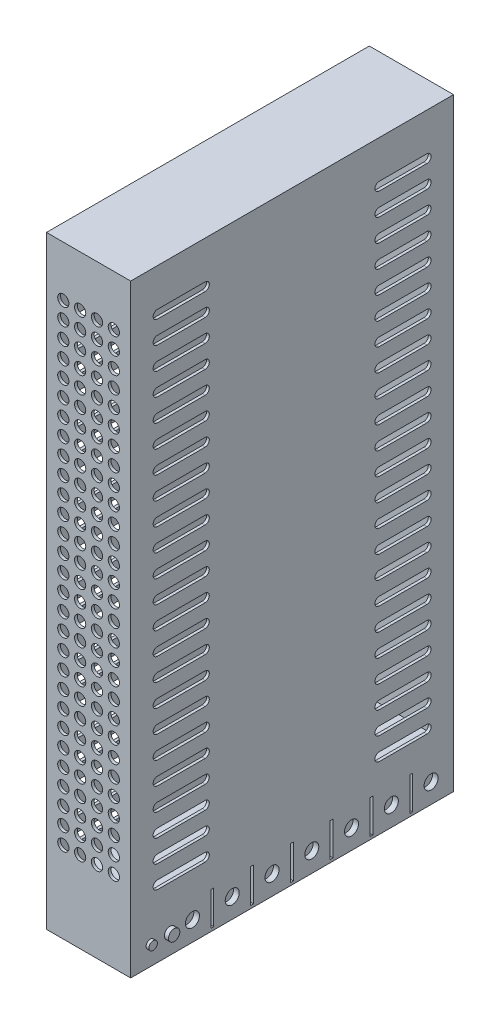
SolidWorks part; units mm, degrees
ref_plane "Front Plane" through (0, 0, 0) normal (0, 0, 1) x (1, 0, 0)
ref_plane "Top Plane" through (0, 0, 0) normal (0, 1, 0) x (1, 0, 0)
ref_plane "Right Plane" through (0, 0, 0) normal (1, 0, 0) x (0, 0, -1)
sketch "Sketch1" plane through (0, 0, 0) normal (0, 0, 1) x (1, 0, 0)
  line L1 (-15, 14) -> (15, 14)
  line L2 (-15, 14) -> (-15, 215)
  line L3 (-15, 215) -> (15, 215)
  line L4 (15, 14) -> (15, 215)
extrude "Case" add sketch "Sketch1" along normal blind 115
shell "Case_shell" thickness 1
sketch "Sketch2" plane through (0, 0, 0) normal (0, 0, 1) x (1, 0, 0)
  line L1 (-15, 0) -> (15, 0)
  line L2 (-15, 0) -> (-15, 14)
  line L3 (-15, 14) -> (15, 14)
  line L4 (15, 0) -> (15, 14)
extrude "Terminal_block" add sketch "Sketch2" along normal blind 115
ref_plane "Plane_x15" through (15, 0, 0) normal (1, 0, 0) x (0, 0, -1)
sketch "Sketch3" plane through (15, 0, 0) normal (1, 0, 0) x (0, 0, -1)
  circle A0 centre (-101, 7) radius 2
extrude "Pot" add sketch "Sketch3" along normal blind 1.5
sketch "Sketch4" plane through (15, 0, 0) normal (1, 0, 0) x (0, 0, -1)
  circle A0 centre (-108, 7) radius 1.5
extrude "LED" add sketch "Sketch4" along normal blind 1
ref_plane "Plane_z115" through (0, 0, 115) normal (0, 0, 1) x (1, 0, 0)
sketch "Sketch5" plane through (0, 0, 115) normal (0, 0, 1) x (1, 0, 0)
  circle A0 centre (-9, 29) radius 2
  circle A1 centre (-9, 35) radius 2
  circle A2 centre (-9, 41) radius 2
  circle A3 centre (-9, 47) radius 2
  circle A4 centre (-9, 53) radius 2
  circle A5 centre (-9, 59) radius 2
  circle A6 centre (-9, 65) radius 2
  circle A7 centre (-9, 71) radius 2
  circle A8 centre (-9, 77) radius 2
  circle A9 centre (-9, 83) radius 2
  circle A10 centre (-9, 89) radius 2
  circle A11 centre (-9, 95) radius 2
  circle A12 centre (-9, 101) radius 2
  circle A13 centre (-9, 107) radius 2
  circle A14 centre (-9, 113) radius 2
  circle A15 centre (-9, 119) radius 2
  circle A16 centre (-9, 125) radius 2
  circle A17 centre (-9, 131) radius 2
  circle A18 centre (-9, 137) radius 2
  circle A19 centre (-9, 143) radius 2
  circle A20 centre (-9, 149) radius 2
  circle A21 centre (-9, 155) radius 2
  circle A22 centre (-9, 161) radius 2
  circle A23 centre (-9, 167) radius 2
  circle A24 centre (-9, 173) radius 2
  circle A25 centre (-9, 179) radius 2
  circle A26 centre (-9, 185) radius 2
  circle A27 centre (-9, 191) radius 2
  circle A28 centre (-9, 197) radius 2
  circle A29 centre (-3, 29) radius 2
  circle A30 centre (-3, 35) radius 2
  circle A31 centre (-3, 41) radius 2
  circle A32 centre (-3, 47) radius 2
  circle A33 centre (-3, 53) radius 2
  circle A34 centre (-3, 59) radius 2
  circle A35 centre (-3, 65) radius 2
  circle A36 centre (-3, 71) radius 2
  circle A37 centre (-3, 77) radius 2
  circle A38 centre (-3, 83) radius 2
  circle A39 centre (-3, 89) radius 2
  circle A40 centre (-3, 95) radius 2
  circle A41 centre (-3, 101) radius 2
  circle A42 centre (-3, 107) radius 2
  circle A43 centre (-3, 113) radius 2
  circle A44 centre (-3, 119) radius 2
  circle A45 centre (-3, 125) radius 2
  circle A46 centre (-3, 131) radius 2
  circle A47 centre (-3, 137) radius 2
  circle A48 centre (-3, 143) radius 2
  circle A49 centre (-3, 149) radius 2
  circle A50 centre (-3, 155) radius 2
  circle A51 centre (-3, 161) radius 2
  circle A52 centre (-3, 167) radius 2
  circle A53 centre (-3, 173) radius 2
  circle A54 centre (-3, 179) radius 2
  circle A55 centre (-3, 185) radius 2
  circle A56 centre (-3, 191) radius 2
  circle A57 centre (-3, 197) radius 2
  circle A58 centre (3, 29) radius 2
  circle A59 centre (3, 35) radius 2
  circle A60 centre (3, 41) radius 2
  circle A61 centre (3, 47) radius 2
  circle A62 centre (3, 53) radius 2
  circle A63 centre (3, 59) radius 2
  circle A64 centre (3, 65) radius 2
  circle A65 centre (3, 71) radius 2
  circle A66 centre (3, 77) radius 2
  circle A67 centre (3, 83) radius 2
  circle A68 centre (3, 89) radius 2
  circle A69 centre (3, 95) radius 2
  circle A70 centre (3, 101) radius 2
  circle A71 centre (3, 107) radius 2
  circle A72 centre (3, 113) radius 2
  circle A73 centre (3, 119) radius 2
  circle A74 centre (3, 125) radius 2
  circle A75 centre (3, 131) radius 2
  circle A76 centre (3, 137) radius 2
  circle A77 centre (3, 143) radius 2
  circle A78 centre (3, 149) radius 2
  circle A79 centre (3, 155) radius 2
  circle A80 centre (3, 161) radius 2
  circle A81 centre (3, 167) radius 2
  circle A82 centre (3, 173) radius 2
  circle A83 centre (3, 179) radius 2
  circle A84 centre (3, 185) radius 2
  circle A85 centre (3, 191) radius 2
  circle A86 centre (3, 197) radius 2
  circle A87 centre (9, 29) radius 2
  circle A88 centre (9, 35) radius 2
  circle A89 centre (9, 41) radius 2
  circle A90 centre (9, 47) radius 2
  circle A91 centre (9, 53) radius 2
  circle A92 centre (9, 59) radius 2
  circle A93 centre (9, 65) radius 2
  circle A94 centre (9, 71) radius 2
  circle A95 centre (9, 77) radius 2
  circle A96 centre (9, 83) radius 2
  circle A97 centre (9, 89) radius 2
  circle A98 centre (9, 95) radius 2
  circle A99 centre (9, 101) radius 2
  circle A100 centre (9, 107) radius 2
  circle A101 centre (9, 113) radius 2
  circle A102 centre (9, 119) radius 2
  circle A103 centre (9, 125) radius 2
  circle A104 centre (9, 131) radius 2
  circle A105 centre (9, 137) radius 2
  circle A106 centre (9, 143) radius 2
  circle A107 centre (9, 149) radius 2
  circle A108 centre (9, 155) radius 2
  circle A109 centre (9, 161) radius 2
  circle A110 centre (9, 167) radius 2
  circle A111 centre (9, 173) radius 2
  circle A112 centre (9, 179) radius 2
  circle A113 centre (9, 185) radius 2
  circle A114 centre (9, 191) radius 2
  circle A115 centre (9, 197) radius 2
extrude "Perforation" cut sketch "Sketch5" against normal blind 1
sketch "Sketch6" plane through (15, 0, 0) normal (1, 0, 0) x (0, 0, -1)
  line L0 (-9.5, 24) -> (-26.5, 24) construction
  line L1 (-9.5, 22.5) -> (-26.5, 22.5)
  line L2 (-9.5, 25.5) -> (-26.5, 25.5)
  line L3 (-88.5, 24) -> (-105.5, 24) construction
  line L4 (-88.5, 22.5) -> (-105.5, 22.5)
  line L5 (-88.5, 25.5) -> (-105.5, 25.5)
  line L6 (-9.5, 32) -> (-26.5, 32) construction
  line L7 (-9.5, 30.5) -> (-26.5, 30.5)
  line L8 (-9.5, 33.5) -> (-26.5, 33.5)
  line L9 (-88.5, 32) -> (-105.5, 32) construction
  line L10 (-88.5, 30.5) -> (-105.5, 30.5)
  line L11 (-88.5, 33.5) -> (-105.5, 33.5)
  line L12 (-9.5, 40) -> (-26.5, 40) construction
  line L13 (-9.5, 38.5) -> (-26.5, 38.5)
  line L14 (-9.5, 41.5) -> (-26.5, 41.5)
  line L15 (-88.5, 40) -> (-105.5, 40) construction
  line L16 (-88.5, 38.5) -> (-105.5, 38.5)
  line L17 (-88.5, 41.5) -> (-105.5, 41.5)
  line L18 (-9.5, 48) -> (-26.5, 48) construction
  line L19 (-9.5, 46.5) -> (-26.5, 46.5)
  line L20 (-9.5, 49.5) -> (-26.5, 49.5)
  line L21 (-88.5, 48) -> (-105.5, 48) construction
  line L22 (-88.5, 46.5) -> (-105.5, 46.5)
  line L23 (-88.5, 49.5) -> (-105.5, 49.5)
  line L24 (-9.5, 56) -> (-26.5, 56) construction
  line L25 (-9.5, 54.5) -> (-26.5, 54.5)
  line L26 (-9.5, 57.5) -> (-26.5, 57.5)
  line L27 (-88.5, 56) -> (-105.5, 56) construction
  line L28 (-88.5, 54.5) -> (-105.5, 54.5)
  line L29 (-88.5, 57.5) -> (-105.5, 57.5)
  line L30 (-9.5, 64) -> (-26.5, 64) construction
  line L31 (-9.5, 62.5) -> (-26.5, 62.5)
  line L32 (-9.5, 65.5) -> (-26.5, 65.5)
  line L33 (-88.5, 64) -> (-105.5, 64) construction
  line L34 (-88.5, 62.5) -> (-105.5, 62.5)
  line L35 (-88.5, 65.5) -> (-105.5, 65.5)
  line L36 (-9.5, 72) -> (-26.5, 72) construction
  line L37 (-9.5, 70.5) -> (-26.5, 70.5)
  line L38 (-9.5, 73.5) -> (-26.5, 73.5)
  line L39 (-88.5, 72) -> (-105.5, 72) construction
  line L40 (-88.5, 70.5) -> (-105.5, 70.5)
  line L41 (-88.5, 73.5) -> (-105.5, 73.5)
  line L42 (-9.5, 80) -> (-26.5, 80) construction
  line L43 (-9.5, 78.5) -> (-26.5, 78.5)
  line L44 (-9.5, 81.5) -> (-26.5, 81.5)
  line L45 (-88.5, 80) -> (-105.5, 80) construction
  line L46 (-88.5, 78.5) -> (-105.5, 78.5)
  line L47 (-88.5, 81.5) -> (-105.5, 81.5)
  line L48 (-9.5, 88) -> (-26.5, 88) construction
  line L49 (-9.5, 86.5) -> (-26.5, 86.5)
  line L50 (-9.5, 89.5) -> (-26.5, 89.5)
  line L51 (-88.5, 88) -> (-105.5, 88) construction
  line L52 (-88.5, 86.5) -> (-105.5, 86.5)
  line L53 (-88.5, 89.5) -> (-105.5, 89.5)
  line L54 (-9.5, 96) -> (-26.5, 96) construction
  line L55 (-9.5, 94.5) -> (-26.5, 94.5)
  line L56 (-9.5, 97.5) -> (-26.5, 97.5)
  line L57 (-88.5, 96) -> (-105.5, 96) construction
  line L58 (-88.5, 94.5) -> (-105.5, 94.5)
  line L59 (-88.5, 97.5) -> (-105.5, 97.5)
  line L60 (-9.5, 104) -> (-26.5, 104) construction
  line L61 (-9.5, 102.5) -> (-26.5, 102.5)
  line L62 (-9.5, 105.5) -> (-26.5, 105.5)
  line L63 (-88.5, 104) -> (-105.5, 104) construction
  line L64 (-88.5, 102.5) -> (-105.5, 102.5)
  line L65 (-88.5, 105.5) -> (-105.5, 105.5)
  line L66 (-9.5, 112) -> (-26.5, 112) construction
  line L67 (-9.5, 110.5) -> (-26.5, 110.5)
  line L68 (-9.5, 113.5) -> (-26.5, 113.5)
  line L69 (-88.5, 112) -> (-105.5, 112) construction
  line L70 (-88.5, 110.5) -> (-105.5, 110.5)
  line L71 (-88.5, 113.5) -> (-105.5, 113.5)
  line L72 (-9.5, 120) -> (-26.5, 120) construction
  line L73 (-9.5, 118.5) -> (-26.5, 118.5)
  line L74 (-9.5, 121.5) -> (-26.5, 121.5)
  line L75 (-88.5, 120) -> (-105.5, 120) construction
  line L76 (-88.5, 118.5) -> (-105.5, 118.5)
  line L77 (-88.5, 121.5) -> (-105.5, 121.5)
  line L78 (-9.5, 128) -> (-26.5, 128) construction
  line L79 (-9.5, 126.5) -> (-26.5, 126.5)
  line L80 (-9.5, 129.5) -> (-26.5, 129.5)
  line L81 (-88.5, 128) -> (-105.5, 128) construction
  line L82 (-88.5, 126.5) -> (-105.5, 126.5)
  line L83 (-88.5, 129.5) -> (-105.5, 129.5)
  line L84 (-9.5, 136) -> (-26.5, 136) construction
  line L85 (-9.5, 134.5) -> (-26.5, 134.5)
  line L86 (-9.5, 137.5) -> (-26.5, 137.5)
  line L87 (-88.5, 136) -> (-105.5, 136) construction
  line L88 (-88.5, 134.5) -> (-105.5, 134.5)
  line L89 (-88.5, 137.5) -> (-105.5, 137.5)
  line L90 (-9.5, 144) -> (-26.5, 144) construction
  line L91 (-9.5, 142.5) -> (-26.5, 142.5)
  line L92 (-9.5, 145.5) -> (-26.5, 145.5)
  line L93 (-88.5, 144) -> (-105.5, 144) construction
  line L94 (-88.5, 142.5) -> (-105.5, 142.5)
  line L95 (-88.5, 145.5) -> (-105.5, 145.5)
  line L96 (-9.5, 152) -> (-26.5, 152) construction
  line L97 (-9.5, 150.5) -> (-26.5, 150.5)
  line L98 (-9.5, 153.5) -> (-26.5, 153.5)
  line L99 (-88.5, 152) -> (-105.5, 152) construction
  line L100 (-88.5, 150.5) -> (-105.5, 150.5)
  line L101 (-88.5, 153.5) -> (-105.5, 153.5)
  line L102 (-9.5, 160) -> (-26.5, 160) construction
  line L103 (-9.5, 158.5) -> (-26.5, 158.5)
  line L104 (-9.5, 161.5) -> (-26.5, 161.5)
  line L105 (-88.5, 160) -> (-105.5, 160) construction
  line L106 (-88.5, 158.5) -> (-105.5, 158.5)
  line L107 (-88.5, 161.5) -> (-105.5, 161.5)
  line L108 (-9.5, 168) -> (-26.5, 168) construction
  line L109 (-9.5, 166.5) -> (-26.5, 166.5)
  line L110 (-9.5, 169.5) -> (-26.5, 169.5)
  line L111 (-88.5, 168) -> (-105.5, 168) construction
  line L112 (-88.5, 166.5) -> (-105.5, 166.5)
  line L113 (-88.5, 169.5) -> (-105.5, 169.5)
  line L114 (-9.5, 176) -> (-26.5, 176) construction
  line L115 (-9.5, 174.5) -> (-26.5, 174.5)
  line L116 (-9.5, 177.5) -> (-26.5, 177.5)
  line L117 (-88.5, 176) -> (-105.5, 176) construction
  line L118 (-88.5, 174.5) -> (-105.5, 174.5)
  line L119 (-88.5, 177.5) -> (-105.5, 177.5)
  line L120 (-9.5, 184) -> (-26.5, 184) construction
  line L121 (-9.5, 182.5) -> (-26.5, 182.5)
  line L122 (-9.5, 185.5) -> (-26.5, 185.5)
  line L123 (-88.5, 184) -> (-105.5, 184) construction
  line L124 (-88.5, 182.5) -> (-105.5, 182.5)
  line L125 (-88.5, 185.5) -> (-105.5, 185.5)
  line L126 (-9.5, 192) -> (-26.5, 192) construction
  line L127 (-9.5, 190.5) -> (-26.5, 190.5)
  line L128 (-9.5, 193.5) -> (-26.5, 193.5)
  line L129 (-88.5, 192) -> (-105.5, 192) construction
  line L130 (-88.5, 190.5) -> (-105.5, 190.5)
  line L131 (-88.5, 193.5) -> (-105.5, 193.5)
  line L132 (-9.5, 200) -> (-26.5, 200) construction
  line L133 (-9.5, 198.5) -> (-26.5, 198.5)
  line L134 (-9.5, 201.5) -> (-26.5, 201.5)
  line L135 (-88.5, 200) -> (-105.5, 200) construction
  line L136 (-88.5, 198.5) -> (-105.5, 198.5)
  line L137 (-88.5, 201.5) -> (-105.5, 201.5)
  arc A0 (-9.5, 22.5) -> (-9.5, 25.5) centre (-9.5, 24) ccw
  arc A1 (-26.5, 25.5) -> (-26.5, 22.5) centre (-26.5, 24) ccw
  arc A2 (-88.5, 22.5) -> (-88.5, 25.5) centre (-88.5, 24) ccw
  arc A3 (-105.5, 25.5) -> (-105.5, 22.5) centre (-105.5, 24) ccw
  arc A4 (-9.5, 30.5) -> (-9.5, 33.5) centre (-9.5, 32) ccw
  arc A5 (-26.5, 33.5) -> (-26.5, 30.5) centre (-26.5, 32) ccw
  arc A6 (-88.5, 30.5) -> (-88.5, 33.5) centre (-88.5, 32) ccw
  arc A7 (-105.5, 33.5) -> (-105.5, 30.5) centre (-105.5, 32) ccw
  arc A8 (-9.5, 38.5) -> (-9.5, 41.5) centre (-9.5, 40) ccw
  arc A9 (-26.5, 41.5) -> (-26.5, 38.5) centre (-26.5, 40) ccw
  arc A10 (-88.5, 38.5) -> (-88.5, 41.5) centre (-88.5, 40) ccw
  arc A11 (-105.5, 41.5) -> (-105.5, 38.5) centre (-105.5, 40) ccw
  arc A12 (-9.5, 46.5) -> (-9.5, 49.5) centre (-9.5, 48) ccw
  arc A13 (-26.5, 49.5) -> (-26.5, 46.5) centre (-26.5, 48) ccw
  arc A14 (-88.5, 46.5) -> (-88.5, 49.5) centre (-88.5, 48) ccw
  arc A15 (-105.5, 49.5) -> (-105.5, 46.5) centre (-105.5, 48) ccw
  arc A16 (-9.5, 54.5) -> (-9.5, 57.5) centre (-9.5, 56) ccw
  arc A17 (-26.5, 57.5) -> (-26.5, 54.5) centre (-26.5, 56) ccw
  arc A18 (-88.5, 54.5) -> (-88.5, 57.5) centre (-88.5, 56) ccw
  arc A19 (-105.5, 57.5) -> (-105.5, 54.5) centre (-105.5, 56) ccw
  arc A20 (-9.5, 62.5) -> (-9.5, 65.5) centre (-9.5, 64) ccw
  arc A21 (-26.5, 65.5) -> (-26.5, 62.5) centre (-26.5, 64) ccw
  arc A22 (-88.5, 62.5) -> (-88.5, 65.5) centre (-88.5, 64) ccw
  arc A23 (-105.5, 65.5) -> (-105.5, 62.5) centre (-105.5, 64) ccw
  arc A24 (-9.5, 70.5) -> (-9.5, 73.5) centre (-9.5, 72) ccw
  arc A25 (-26.5, 73.5) -> (-26.5, 70.5) centre (-26.5, 72) ccw
  arc A26 (-88.5, 70.5) -> (-88.5, 73.5) centre (-88.5, 72) ccw
  arc A27 (-105.5, 73.5) -> (-105.5, 70.5) centre (-105.5, 72) ccw
  arc A28 (-9.5, 78.5) -> (-9.5, 81.5) centre (-9.5, 80) ccw
  arc A29 (-26.5, 81.5) -> (-26.5, 78.5) centre (-26.5, 80) ccw
  arc A30 (-88.5, 78.5) -> (-88.5, 81.5) centre (-88.5, 80) ccw
  arc A31 (-105.5, 81.5) -> (-105.5, 78.5) centre (-105.5, 80) ccw
  arc A32 (-9.5, 86.5) -> (-9.5, 89.5) centre (-9.5, 88) ccw
  arc A33 (-26.5, 89.5) -> (-26.5, 86.5) centre (-26.5, 88) ccw
  arc A34 (-88.5, 86.5) -> (-88.5, 89.5) centre (-88.5, 88) ccw
  arc A35 (-105.5, 89.5) -> (-105.5, 86.5) centre (-105.5, 88) ccw
  arc A36 (-9.5, 94.5) -> (-9.5, 97.5) centre (-9.5, 96) ccw
  arc A37 (-26.5, 97.5) -> (-26.5, 94.5) centre (-26.5, 96) ccw
  arc A38 (-88.5, 94.5) -> (-88.5, 97.5) centre (-88.5, 96) ccw
  arc A39 (-105.5, 97.5) -> (-105.5, 94.5) centre (-105.5, 96) ccw
  arc A40 (-9.5, 102.5) -> (-9.5, 105.5) centre (-9.5, 104) ccw
  arc A41 (-26.5, 105.5) -> (-26.5, 102.5) centre (-26.5, 104) ccw
  arc A42 (-88.5, 102.5) -> (-88.5, 105.5) centre (-88.5, 104) ccw
  arc A43 (-105.5, 105.5) -> (-105.5, 102.5) centre (-105.5, 104) ccw
  arc A44 (-9.5, 110.5) -> (-9.5, 113.5) centre (-9.5, 112) ccw
  arc A45 (-26.5, 113.5) -> (-26.5, 110.5) centre (-26.5, 112) ccw
  arc A46 (-88.5, 110.5) -> (-88.5, 113.5) centre (-88.5, 112) ccw
  arc A47 (-105.5, 113.5) -> (-105.5, 110.5) centre (-105.5, 112) ccw
  arc A48 (-9.5, 118.5) -> (-9.5, 121.5) centre (-9.5, 120) ccw
  arc A49 (-26.5, 121.5) -> (-26.5, 118.5) centre (-26.5, 120) ccw
  arc A50 (-88.5, 118.5) -> (-88.5, 121.5) centre (-88.5, 120) ccw
  arc A51 (-105.5, 121.5) -> (-105.5, 118.5) centre (-105.5, 120) ccw
  arc A52 (-9.5, 126.5) -> (-9.5, 129.5) centre (-9.5, 128) ccw
  arc A53 (-26.5, 129.5) -> (-26.5, 126.5) centre (-26.5, 128) ccw
  arc A54 (-88.5, 126.5) -> (-88.5, 129.5) centre (-88.5, 128) ccw
  arc A55 (-105.5, 129.5) -> (-105.5, 126.5) centre (-105.5, 128) ccw
  arc A56 (-9.5, 134.5) -> (-9.5, 137.5) centre (-9.5, 136) ccw
  arc A57 (-26.5, 137.5) -> (-26.5, 134.5) centre (-26.5, 136) ccw
  arc A58 (-88.5, 134.5) -> (-88.5, 137.5) centre (-88.5, 136) ccw
  arc A59 (-105.5, 137.5) -> (-105.5, 134.5) centre (-105.5, 136) ccw
  arc A60 (-9.5, 142.5) -> (-9.5, 145.5) centre (-9.5, 144) ccw
  arc A61 (-26.5, 145.5) -> (-26.5, 142.5) centre (-26.5, 144) ccw
  arc A62 (-88.5, 142.5) -> (-88.5, 145.5) centre (-88.5, 144) ccw
  arc A63 (-105.5, 145.5) -> (-105.5, 142.5) centre (-105.5, 144) ccw
  arc A64 (-9.5, 150.5) -> (-9.5, 153.5) centre (-9.5, 152) ccw
  arc A65 (-26.5, 153.5) -> (-26.5, 150.5) centre (-26.5, 152) ccw
  arc A66 (-88.5, 150.5) -> (-88.5, 153.5) centre (-88.5, 152) ccw
  arc A67 (-105.5, 153.5) -> (-105.5, 150.5) centre (-105.5, 152) ccw
  arc A68 (-9.5, 158.5) -> (-9.5, 161.5) centre (-9.5, 160) ccw
  arc A69 (-26.5, 161.5) -> (-26.5, 158.5) centre (-26.5, 160) ccw
  arc A70 (-88.5, 158.5) -> (-88.5, 161.5) centre (-88.5, 160) ccw
  arc A71 (-105.5, 161.5) -> (-105.5, 158.5) centre (-105.5, 160) ccw
  arc A72 (-9.5, 166.5) -> (-9.5, 169.5) centre (-9.5, 168) ccw
  arc A73 (-26.5, 169.5) -> (-26.5, 166.5) centre (-26.5, 168) ccw
  arc A74 (-88.5, 166.5) -> (-88.5, 169.5) centre (-88.5, 168) ccw
  arc A75 (-105.5, 169.5) -> (-105.5, 166.5) centre (-105.5, 168) ccw
  arc A76 (-9.5, 174.5) -> (-9.5, 177.5) centre (-9.5, 176) ccw
  arc A77 (-26.5, 177.5) -> (-26.5, 174.5) centre (-26.5, 176) ccw
  arc A78 (-88.5, 174.5) -> (-88.5, 177.5) centre (-88.5, 176) ccw
  arc A79 (-105.5, 177.5) -> (-105.5, 174.5) centre (-105.5, 176) ccw
  arc A80 (-9.5, 182.5) -> (-9.5, 185.5) centre (-9.5, 184) ccw
  arc A81 (-26.5, 185.5) -> (-26.5, 182.5) centre (-26.5, 184) ccw
  arc A82 (-88.5, 182.5) -> (-88.5, 185.5) centre (-88.5, 184) ccw
  arc A83 (-105.5, 185.5) -> (-105.5, 182.5) centre (-105.5, 184) ccw
  arc A84 (-9.5, 190.5) -> (-9.5, 193.5) centre (-9.5, 192) ccw
  arc A85 (-26.5, 193.5) -> (-26.5, 190.5) centre (-26.5, 192) ccw
  arc A86 (-88.5, 190.5) -> (-88.5, 193.5) centre (-88.5, 192) ccw
  arc A87 (-105.5, 193.5) -> (-105.5, 190.5) centre (-105.5, 192) ccw
  arc A88 (-9.5, 198.5) -> (-9.5, 201.5) centre (-9.5, 200) ccw
  arc A89 (-26.5, 201.5) -> (-26.5, 198.5) centre (-26.5, 200) ccw
  arc A90 (-88.5, 198.5) -> (-88.5, 201.5) centre (-88.5, 200) ccw
  arc A91 (-105.5, 201.5) -> (-105.5, 198.5) centre (-105.5, 200) ccw
  point P2 (-18, 24)
  point P7 (-97, 24)
  point P14 (-18, 32)
  point P21 (-97, 32)
  point P28 (-18, 40)
  point P35 (-97, 40)
  point P42 (-18, 48)
  point P49 (-97, 48)
  point P56 (-18, 56)
  point P63 (-97, 56)
  point P70 (-18, 64)
  point P77 (-97, 64)
  point P84 (-18, 72)
  point P91 (-97, 72)
  point P98 (-18, 80)
  point P105 (-97, 80)
  point P112 (-18, 88)
  point P119 (-97, 88)
  point P126 (-18, 96)
  point P133 (-97, 96)
  point P140 (-18, 104)
  point P147 (-97, 104)
  point P154 (-18, 112)
  point P161 (-97, 112)
  point P168 (-18, 120)
  point P175 (-97, 120)
  point P182 (-18, 128)
  point P189 (-97, 128)
  point P196 (-18, 136)
  point P203 (-97, 136)
  point P210 (-18, 144)
  point P217 (-97, 144)
  point P224 (-18, 152)
  point P231 (-97, 152)
  point P238 (-18, 160)
  point P245 (-97, 160)
  point P252 (-18, 168)
  point P259 (-97, 168)
  point P266 (-18, 176)
  point P273 (-97, 176)
  point P280 (-18, 184)
  point P287 (-97, 184)
  point P294 (-18, 192)
  point P301 (-97, 192)
  point P308 (-18, 200)
  point P315 (-97, 200)
  point P322 (0, 0)
extrude "Vents_R" cut sketch "Sketch6" against normal blind 1
ref_plane "Plane_xm15" through (-15, 0, 0) normal (1, 0, 0) x (0, 0, -1)
sketch "Sketch7" plane through (-15, 0, 0) normal (1, 0, 0) x (0, 0, -1)
  line L0 (-9.5, 24) -> (-26.5, 24) construction
  line L1 (-9.5, 22.5) -> (-26.5, 22.5)
  line L2 (-9.5, 25.5) -> (-26.5, 25.5)
  line L3 (-88.5, 24) -> (-105.5, 24) construction
  line L4 (-88.5, 22.5) -> (-105.5, 22.5)
  line L5 (-88.5, 25.5) -> (-105.5, 25.5)
  line L6 (-9.5, 32) -> (-26.5, 32) construction
  line L7 (-9.5, 30.5) -> (-26.5, 30.5)
  line L8 (-9.5, 33.5) -> (-26.5, 33.5)
  line L9 (-88.5, 32) -> (-105.5, 32) construction
  line L10 (-88.5, 30.5) -> (-105.5, 30.5)
  line L11 (-88.5, 33.5) -> (-105.5, 33.5)
  line L12 (-9.5, 40) -> (-26.5, 40) construction
  line L13 (-9.5, 38.5) -> (-26.5, 38.5)
  line L14 (-9.5, 41.5) -> (-26.5, 41.5)
  line L15 (-88.5, 40) -> (-105.5, 40) construction
  line L16 (-88.5, 38.5) -> (-105.5, 38.5)
  line L17 (-88.5, 41.5) -> (-105.5, 41.5)
  line L18 (-9.5, 48) -> (-26.5, 48) construction
  line L19 (-9.5, 46.5) -> (-26.5, 46.5)
  line L20 (-9.5, 49.5) -> (-26.5, 49.5)
  line L21 (-88.5, 48) -> (-105.5, 48) construction
  line L22 (-88.5, 46.5) -> (-105.5, 46.5)
  line L23 (-88.5, 49.5) -> (-105.5, 49.5)
  line L24 (-9.5, 56) -> (-26.5, 56) construction
  line L25 (-9.5, 54.5) -> (-26.5, 54.5)
  line L26 (-9.5, 57.5) -> (-26.5, 57.5)
  line L27 (-88.5, 56) -> (-105.5, 56) construction
  line L28 (-88.5, 54.5) -> (-105.5, 54.5)
  line L29 (-88.5, 57.5) -> (-105.5, 57.5)
  line L30 (-9.5, 64) -> (-26.5, 64) construction
  line L31 (-9.5, 62.5) -> (-26.5, 62.5)
  line L32 (-9.5, 65.5) -> (-26.5, 65.5)
  line L33 (-88.5, 64) -> (-105.5, 64) construction
  line L34 (-88.5, 62.5) -> (-105.5, 62.5)
  line L35 (-88.5, 65.5) -> (-105.5, 65.5)
  line L36 (-9.5, 72) -> (-26.5, 72) construction
  line L37 (-9.5, 70.5) -> (-26.5, 70.5)
  line L38 (-9.5, 73.5) -> (-26.5, 73.5)
  line L39 (-88.5, 72) -> (-105.5, 72) construction
  line L40 (-88.5, 70.5) -> (-105.5, 70.5)
  line L41 (-88.5, 73.5) -> (-105.5, 73.5)
  line L42 (-9.5, 80) -> (-26.5, 80) construction
  line L43 (-9.5, 78.5) -> (-26.5, 78.5)
  line L44 (-9.5, 81.5) -> (-26.5, 81.5)
  line L45 (-88.5, 80) -> (-105.5, 80) construction
  line L46 (-88.5, 78.5) -> (-105.5, 78.5)
  line L47 (-88.5, 81.5) -> (-105.5, 81.5)
  line L48 (-9.5, 88) -> (-26.5, 88) construction
  line L49 (-9.5, 86.5) -> (-26.5, 86.5)
  line L50 (-9.5, 89.5) -> (-26.5, 89.5)
  line L51 (-88.5, 88) -> (-105.5, 88) construction
  line L52 (-88.5, 86.5) -> (-105.5, 86.5)
  line L53 (-88.5, 89.5) -> (-105.5, 89.5)
  line L54 (-9.5, 96) -> (-26.5, 96) construction
  line L55 (-9.5, 94.5) -> (-26.5, 94.5)
  line L56 (-9.5, 97.5) -> (-26.5, 97.5)
  line L57 (-88.5, 96) -> (-105.5, 96) construction
  line L58 (-88.5, 94.5) -> (-105.5, 94.5)
  line L59 (-88.5, 97.5) -> (-105.5, 97.5)
  line L60 (-9.5, 104) -> (-26.5, 104) construction
  line L61 (-9.5, 102.5) -> (-26.5, 102.5)
  line L62 (-9.5, 105.5) -> (-26.5, 105.5)
  line L63 (-88.5, 104) -> (-105.5, 104) construction
  line L64 (-88.5, 102.5) -> (-105.5, 102.5)
  line L65 (-88.5, 105.5) -> (-105.5, 105.5)
  line L66 (-9.5, 112) -> (-26.5, 112) construction
  line L67 (-9.5, 110.5) -> (-26.5, 110.5)
  line L68 (-9.5, 113.5) -> (-26.5, 113.5)
  line L69 (-88.5, 112) -> (-105.5, 112) construction
  line L70 (-88.5, 110.5) -> (-105.5, 110.5)
  line L71 (-88.5, 113.5) -> (-105.5, 113.5)
  line L72 (-9.5, 120) -> (-26.5, 120) construction
  line L73 (-9.5, 118.5) -> (-26.5, 118.5)
  line L74 (-9.5, 121.5) -> (-26.5, 121.5)
  line L75 (-88.5, 120) -> (-105.5, 120) construction
  line L76 (-88.5, 118.5) -> (-105.5, 118.5)
  line L77 (-88.5, 121.5) -> (-105.5, 121.5)
  line L78 (-9.5, 128) -> (-26.5, 128) construction
  line L79 (-9.5, 126.5) -> (-26.5, 126.5)
  line L80 (-9.5, 129.5) -> (-26.5, 129.5)
  line L81 (-88.5, 128) -> (-105.5, 128) construction
  line L82 (-88.5, 126.5) -> (-105.5, 126.5)
  line L83 (-88.5, 129.5) -> (-105.5, 129.5)
  line L84 (-9.5, 136) -> (-26.5, 136) construction
  line L85 (-9.5, 134.5) -> (-26.5, 134.5)
  line L86 (-9.5, 137.5) -> (-26.5, 137.5)
  line L87 (-88.5, 136) -> (-105.5, 136) construction
  line L88 (-88.5, 134.5) -> (-105.5, 134.5)
  line L89 (-88.5, 137.5) -> (-105.5, 137.5)
  line L90 (-9.5, 144) -> (-26.5, 144) construction
  line L91 (-9.5, 142.5) -> (-26.5, 142.5)
  line L92 (-9.5, 145.5) -> (-26.5, 145.5)
  line L93 (-88.5, 144) -> (-105.5, 144) construction
  line L94 (-88.5, 142.5) -> (-105.5, 142.5)
  line L95 (-88.5, 145.5) -> (-105.5, 145.5)
  line L96 (-9.5, 152) -> (-26.5, 152) construction
  line L97 (-9.5, 150.5) -> (-26.5, 150.5)
  line L98 (-9.5, 153.5) -> (-26.5, 153.5)
  line L99 (-88.5, 152) -> (-105.5, 152) construction
  line L100 (-88.5, 150.5) -> (-105.5, 150.5)
  line L101 (-88.5, 153.5) -> (-105.5, 153.5)
  line L102 (-9.5, 160) -> (-26.5, 160) construction
  line L103 (-9.5, 158.5) -> (-26.5, 158.5)
  line L104 (-9.5, 161.5) -> (-26.5, 161.5)
  line L105 (-88.5, 160) -> (-105.5, 160) construction
  line L106 (-88.5, 158.5) -> (-105.5, 158.5)
  line L107 (-88.5, 161.5) -> (-105.5, 161.5)
  line L108 (-9.5, 168) -> (-26.5, 168) construction
  line L109 (-9.5, 166.5) -> (-26.5, 166.5)
  line L110 (-9.5, 169.5) -> (-26.5, 169.5)
  line L111 (-88.5, 168) -> (-105.5, 168) construction
  line L112 (-88.5, 166.5) -> (-105.5, 166.5)
  line L113 (-88.5, 169.5) -> (-105.5, 169.5)
  line L114 (-9.5, 176) -> (-26.5, 176) construction
  line L115 (-9.5, 174.5) -> (-26.5, 174.5)
  line L116 (-9.5, 177.5) -> (-26.5, 177.5)
  line L117 (-88.5, 176) -> (-105.5, 176) construction
  line L118 (-88.5, 174.5) -> (-105.5, 174.5)
  line L119 (-88.5, 177.5) -> (-105.5, 177.5)
  line L120 (-9.5, 184) -> (-26.5, 184) construction
  line L121 (-9.5, 182.5) -> (-26.5, 182.5)
  line L122 (-9.5, 185.5) -> (-26.5, 185.5)
  line L123 (-88.5, 184) -> (-105.5, 184) construction
  line L124 (-88.5, 182.5) -> (-105.5, 182.5)
  line L125 (-88.5, 185.5) -> (-105.5, 185.5)
  line L126 (-9.5, 192) -> (-26.5, 192) construction
  line L127 (-9.5, 190.5) -> (-26.5, 190.5)
  line L128 (-9.5, 193.5) -> (-26.5, 193.5)
  line L129 (-88.5, 192) -> (-105.5, 192) construction
  line L130 (-88.5, 190.5) -> (-105.5, 190.5)
  line L131 (-88.5, 193.5) -> (-105.5, 193.5)
  line L132 (-9.5, 200) -> (-26.5, 200) construction
  line L133 (-9.5, 198.5) -> (-26.5, 198.5)
  line L134 (-9.5, 201.5) -> (-26.5, 201.5)
  line L135 (-88.5, 200) -> (-105.5, 200) construction
  line L136 (-88.5, 198.5) -> (-105.5, 198.5)
  line L137 (-88.5, 201.5) -> (-105.5, 201.5)
  arc A0 (-9.5, 22.5) -> (-9.5, 25.5) centre (-9.5, 24) ccw
  arc A1 (-26.5, 25.5) -> (-26.5, 22.5) centre (-26.5, 24) ccw
  arc A2 (-88.5, 22.5) -> (-88.5, 25.5) centre (-88.5, 24) ccw
  arc A3 (-105.5, 25.5) -> (-105.5, 22.5) centre (-105.5, 24) ccw
  arc A4 (-9.5, 30.5) -> (-9.5, 33.5) centre (-9.5, 32) ccw
  arc A5 (-26.5, 33.5) -> (-26.5, 30.5) centre (-26.5, 32) ccw
  arc A6 (-88.5, 30.5) -> (-88.5, 33.5) centre (-88.5, 32) ccw
  arc A7 (-105.5, 33.5) -> (-105.5, 30.5) centre (-105.5, 32) ccw
  arc A8 (-9.5, 38.5) -> (-9.5, 41.5) centre (-9.5, 40) ccw
  arc A9 (-26.5, 41.5) -> (-26.5, 38.5) centre (-26.5, 40) ccw
  arc A10 (-88.5, 38.5) -> (-88.5, 41.5) centre (-88.5, 40) ccw
  arc A11 (-105.5, 41.5) -> (-105.5, 38.5) centre (-105.5, 40) ccw
  arc A12 (-9.5, 46.5) -> (-9.5, 49.5) centre (-9.5, 48) ccw
  arc A13 (-26.5, 49.5) -> (-26.5, 46.5) centre (-26.5, 48) ccw
  arc A14 (-88.5, 46.5) -> (-88.5, 49.5) centre (-88.5, 48) ccw
  arc A15 (-105.5, 49.5) -> (-105.5, 46.5) centre (-105.5, 48) ccw
  arc A16 (-9.5, 54.5) -> (-9.5, 57.5) centre (-9.5, 56) ccw
  arc A17 (-26.5, 57.5) -> (-26.5, 54.5) centre (-26.5, 56) ccw
  arc A18 (-88.5, 54.5) -> (-88.5, 57.5) centre (-88.5, 56) ccw
  arc A19 (-105.5, 57.5) -> (-105.5, 54.5) centre (-105.5, 56) ccw
  arc A20 (-9.5, 62.5) -> (-9.5, 65.5) centre (-9.5, 64) ccw
  arc A21 (-26.5, 65.5) -> (-26.5, 62.5) centre (-26.5, 64) ccw
  arc A22 (-88.5, 62.5) -> (-88.5, 65.5) centre (-88.5, 64) ccw
  arc A23 (-105.5, 65.5) -> (-105.5, 62.5) centre (-105.5, 64) ccw
  arc A24 (-9.5, 70.5) -> (-9.5, 73.5) centre (-9.5, 72) ccw
  arc A25 (-26.5, 73.5) -> (-26.5, 70.5) centre (-26.5, 72) ccw
  arc A26 (-88.5, 70.5) -> (-88.5, 73.5) centre (-88.5, 72) ccw
  arc A27 (-105.5, 73.5) -> (-105.5, 70.5) centre (-105.5, 72) ccw
  arc A28 (-9.5, 78.5) -> (-9.5, 81.5) centre (-9.5, 80) ccw
  arc A29 (-26.5, 81.5) -> (-26.5, 78.5) centre (-26.5, 80) ccw
  arc A30 (-88.5, 78.5) -> (-88.5, 81.5) centre (-88.5, 80) ccw
  arc A31 (-105.5, 81.5) -> (-105.5, 78.5) centre (-105.5, 80) ccw
  arc A32 (-9.5, 86.5) -> (-9.5, 89.5) centre (-9.5, 88) ccw
  arc A33 (-26.5, 89.5) -> (-26.5, 86.5) centre (-26.5, 88) ccw
  arc A34 (-88.5, 86.5) -> (-88.5, 89.5) centre (-88.5, 88) ccw
  arc A35 (-105.5, 89.5) -> (-105.5, 86.5) centre (-105.5, 88) ccw
  arc A36 (-9.5, 94.5) -> (-9.5, 97.5) centre (-9.5, 96) ccw
  arc A37 (-26.5, 97.5) -> (-26.5, 94.5) centre (-26.5, 96) ccw
  arc A38 (-88.5, 94.5) -> (-88.5, 97.5) centre (-88.5, 96) ccw
  arc A39 (-105.5, 97.5) -> (-105.5, 94.5) centre (-105.5, 96) ccw
  arc A40 (-9.5, 102.5) -> (-9.5, 105.5) centre (-9.5, 104) ccw
  arc A41 (-26.5, 105.5) -> (-26.5, 102.5) centre (-26.5, 104) ccw
  arc A42 (-88.5, 102.5) -> (-88.5, 105.5) centre (-88.5, 104) ccw
  arc A43 (-105.5, 105.5) -> (-105.5, 102.5) centre (-105.5, 104) ccw
  arc A44 (-9.5, 110.5) -> (-9.5, 113.5) centre (-9.5, 112) ccw
  arc A45 (-26.5, 113.5) -> (-26.5, 110.5) centre (-26.5, 112) ccw
  arc A46 (-88.5, 110.5) -> (-88.5, 113.5) centre (-88.5, 112) ccw
  arc A47 (-105.5, 113.5) -> (-105.5, 110.5) centre (-105.5, 112) ccw
  arc A48 (-9.5, 118.5) -> (-9.5, 121.5) centre (-9.5, 120) ccw
  arc A49 (-26.5, 121.5) -> (-26.5, 118.5) centre (-26.5, 120) ccw
  arc A50 (-88.5, 118.5) -> (-88.5, 121.5) centre (-88.5, 120) ccw
  arc A51 (-105.5, 121.5) -> (-105.5, 118.5) centre (-105.5, 120) ccw
  arc A52 (-9.5, 126.5) -> (-9.5, 129.5) centre (-9.5, 128) ccw
  arc A53 (-26.5, 129.5) -> (-26.5, 126.5) centre (-26.5, 128) ccw
  arc A54 (-88.5, 126.5) -> (-88.5, 129.5) centre (-88.5, 128) ccw
  arc A55 (-105.5, 129.5) -> (-105.5, 126.5) centre (-105.5, 128) ccw
  arc A56 (-9.5, 134.5) -> (-9.5, 137.5) centre (-9.5, 136) ccw
  arc A57 (-26.5, 137.5) -> (-26.5, 134.5) centre (-26.5, 136) ccw
  arc A58 (-88.5, 134.5) -> (-88.5, 137.5) centre (-88.5, 136) ccw
  arc A59 (-105.5, 137.5) -> (-105.5, 134.5) centre (-105.5, 136) ccw
  arc A60 (-9.5, 142.5) -> (-9.5, 145.5) centre (-9.5, 144) ccw
  arc A61 (-26.5, 145.5) -> (-26.5, 142.5) centre (-26.5, 144) ccw
  arc A62 (-88.5, 142.5) -> (-88.5, 145.5) centre (-88.5, 144) ccw
  arc A63 (-105.5, 145.5) -> (-105.5, 142.5) centre (-105.5, 144) ccw
  arc A64 (-9.5, 150.5) -> (-9.5, 153.5) centre (-9.5, 152) ccw
  arc A65 (-26.5, 153.5) -> (-26.5, 150.5) centre (-26.5, 152) ccw
  arc A66 (-88.5, 150.5) -> (-88.5, 153.5) centre (-88.5, 152) ccw
  arc A67 (-105.5, 153.5) -> (-105.5, 150.5) centre (-105.5, 152) ccw
  arc A68 (-9.5, 158.5) -> (-9.5, 161.5) centre (-9.5, 160) ccw
  arc A69 (-26.5, 161.5) -> (-26.5, 158.5) centre (-26.5, 160) ccw
  arc A70 (-88.5, 158.5) -> (-88.5, 161.5) centre (-88.5, 160) ccw
  arc A71 (-105.5, 161.5) -> (-105.5, 158.5) centre (-105.5, 160) ccw
  arc A72 (-9.5, 166.5) -> (-9.5, 169.5) centre (-9.5, 168) ccw
  arc A73 (-26.5, 169.5) -> (-26.5, 166.5) centre (-26.5, 168) ccw
  arc A74 (-88.5, 166.5) -> (-88.5, 169.5) centre (-88.5, 168) ccw
  arc A75 (-105.5, 169.5) -> (-105.5, 166.5) centre (-105.5, 168) ccw
  arc A76 (-9.5, 174.5) -> (-9.5, 177.5) centre (-9.5, 176) ccw
  arc A77 (-26.5, 177.5) -> (-26.5, 174.5) centre (-26.5, 176) ccw
  arc A78 (-88.5, 174.5) -> (-88.5, 177.5) centre (-88.5, 176) ccw
  arc A79 (-105.5, 177.5) -> (-105.5, 174.5) centre (-105.5, 176) ccw
  arc A80 (-9.5, 182.5) -> (-9.5, 185.5) centre (-9.5, 184) ccw
  arc A81 (-26.5, 185.5) -> (-26.5, 182.5) centre (-26.5, 184) ccw
  arc A82 (-88.5, 182.5) -> (-88.5, 185.5) centre (-88.5, 184) ccw
  arc A83 (-105.5, 185.5) -> (-105.5, 182.5) centre (-105.5, 184) ccw
  arc A84 (-9.5, 190.5) -> (-9.5, 193.5) centre (-9.5, 192) ccw
  arc A85 (-26.5, 193.5) -> (-26.5, 190.5) centre (-26.5, 192) ccw
  arc A86 (-88.5, 190.5) -> (-88.5, 193.5) centre (-88.5, 192) ccw
  arc A87 (-105.5, 193.5) -> (-105.5, 190.5) centre (-105.5, 192) ccw
  arc A88 (-9.5, 198.5) -> (-9.5, 201.5) centre (-9.5, 200) ccw
  arc A89 (-26.5, 201.5) -> (-26.5, 198.5) centre (-26.5, 200) ccw
  arc A90 (-88.5, 198.5) -> (-88.5, 201.5) centre (-88.5, 200) ccw
  arc A91 (-105.5, 201.5) -> (-105.5, 198.5) centre (-105.5, 200) ccw
  point P2 (-18, 24)
  point P7 (-97, 24)
  point P14 (-18, 32)
  point P21 (-97, 32)
  point P28 (-18, 40)
  point P35 (-97, 40)
  point P42 (-18, 48)
  point P49 (-97, 48)
  point P56 (-18, 56)
  point P63 (-97, 56)
  point P70 (-18, 64)
  point P77 (-97, 64)
  point P84 (-18, 72)
  point P91 (-97, 72)
  point P98 (-18, 80)
  point P105 (-97, 80)
  point P112 (-18, 88)
  point P119 (-97, 88)
  point P126 (-18, 96)
  point P133 (-97, 96)
  point P140 (-18, 104)
  point P147 (-97, 104)
  point P154 (-18, 112)
  point P161 (-97, 112)
  point P168 (-18, 120)
  point P175 (-97, 120)
  point P182 (-18, 128)
  point P189 (-97, 128)
  point P196 (-18, 136)
  point P203 (-97, 136)
  point P210 (-18, 144)
  point P217 (-97, 144)
  point P224 (-18, 152)
  point P231 (-97, 152)
  point P238 (-18, 160)
  point P245 (-97, 160)
  point P252 (-18, 168)
  point P259 (-97, 168)
  point P266 (-18, 176)
  point P273 (-97, 176)
  point P280 (-18, 184)
  point P287 (-97, 184)
  point P294 (-18, 192)
  point P301 (-97, 192)
  point P308 (-18, 200)
  point P315 (-97, 200)
  point P322 (0, 0)
extrude "Vents_L" cut sketch "Sketch7" along normal blind 1
sketch "Sketch8" plane through (15, 0, 0) normal (1, 0, 0) x (0, 0, -1)
  circle A0 centre (-8, 7) radius 2.5
  circle A1 centre (-22.1667, 7) radius 2.5
  circle A2 centre (-36.3333, 7) radius 2.5
  circle A3 centre (-50.5, 7) radius 2.5
  circle A4 centre (-64.6667, 7) radius 2.5
  circle A5 centre (-78.8333, 7) radius 2.5
  circle A6 centre (-93, 7) radius 2.5
extrude "Screws" cut sketch "Sketch8" against normal blind 2
sketch "Sketch9" plane through (15, 0, 0) normal (1, 0, 0) x (0, 0, -1)
  line L1 (-14.5833, 1) -> (-15.5833, 1)
  line L2 (-14.5833, 1) -> (-14.5833, 13)
  line L3 (-14.5833, 13) -> (-15.5833, 13)
  line L4 (-15.5833, 1) -> (-15.5833, 13)
  line L6 (-28.75, 1) -> (-29.75, 1)
  line L7 (-28.75, 1) -> (-28.75, 13)
  line L8 (-28.75, 13) -> (-29.75, 13)
  line L9 (-29.75, 1) -> (-29.75, 13)
  line L11 (-42.9167, 1) -> (-43.9167, 1)
  line L12 (-42.9167, 1) -> (-42.9167, 13)
  line L13 (-42.9167, 13) -> (-43.9167, 13)
  line L14 (-43.9167, 1) -> (-43.9167, 13)
  line L16 (-57.0833, 1) -> (-58.0833, 1)
  line L17 (-57.0833, 1) -> (-57.0833, 13)
  line L18 (-57.0833, 13) -> (-58.0833, 13)
  line L19 (-58.0833, 1) -> (-58.0833, 13)
  line L21 (-71.25, 1) -> (-72.25, 1)
  line L22 (-71.25, 1) -> (-71.25, 13)
  line L23 (-71.25, 13) -> (-72.25, 13)
  line L24 (-72.25, 1) -> (-72.25, 13)
  line L26 (-85.4167, 1) -> (-86.4167, 1)
  line L27 (-85.4167, 1) -> (-85.4167, 13)
  line L28 (-85.4167, 13) -> (-86.4167, 13)
  line L29 (-86.4167, 1) -> (-86.4167, 13)
extrude "Barriers" cut sketch "Sketch9" against normal blind 3
